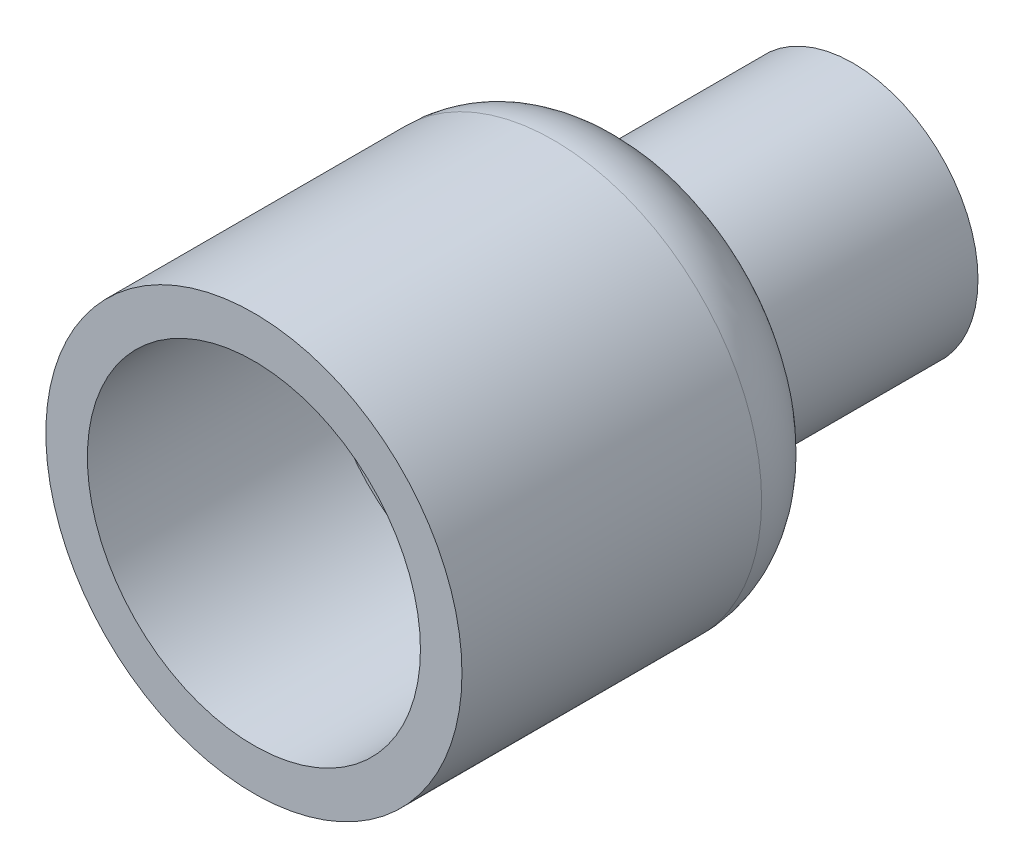
SolidWorks part; units mm, degrees
ref_plane "Front Plane" through (0, 0, 0) normal (0, 0, 1) x (1, 0, 0)
ref_plane "Top Plane" through (0, 0, 0) normal (0, 1, 0) x (1, 0, 0)
ref_plane "Right Plane" through (0, 0, 0) normal (1, 0, 0) x (0, 0, -1)
sketch "Sketch1" plane through (0, 0, 0) normal (0, 0, 1) x (1, 0, 0)
  circle A0 centre (0, 0) radius 7.5
  dimension "D1" = 15
ref_plane "Plane1" through (0, 0, 20) normal (0, 0, 1) x (1, 0, 0)
sketch "Sketch2" plane through (0, 0, 20) normal (0, 0, 1) x (1, 0, 0)
  circle A0 centre (0, 0) radius 12.5
  dimension "D1" = 25
extrude "Boss-Extrude1" add sketch "Sketch1" along normal blind 16 contours A0
extrude "Boss-Extrude2" add sketch "Sketch2" along normal blind 16 and the other way blind 7 contours A0
fillet "Fillet1" radius 5 1 edges at (12.5, 0, 13)
sketch "Sketch3" plane through (0, 0, 0) normal (0, 0, -1) x (-1, 0, 0)
  circle A0 centre (0, 0) radius 5.005
  dimension "D1" = 10.01
sketch "Sketch4" plane through (0, 0, 36) normal (0, 0, 1) x (1, 0, 0)
  circle A0 centre (0, 0) radius 10.005
  dimension "D1" = 20.01
extrude "Cut-Extrude1" cut sketch "Sketch4" against normal blind 14
extrude "Cut-Extrude2" cut sketch "Sketch3" against normal blind 10 contours A0
